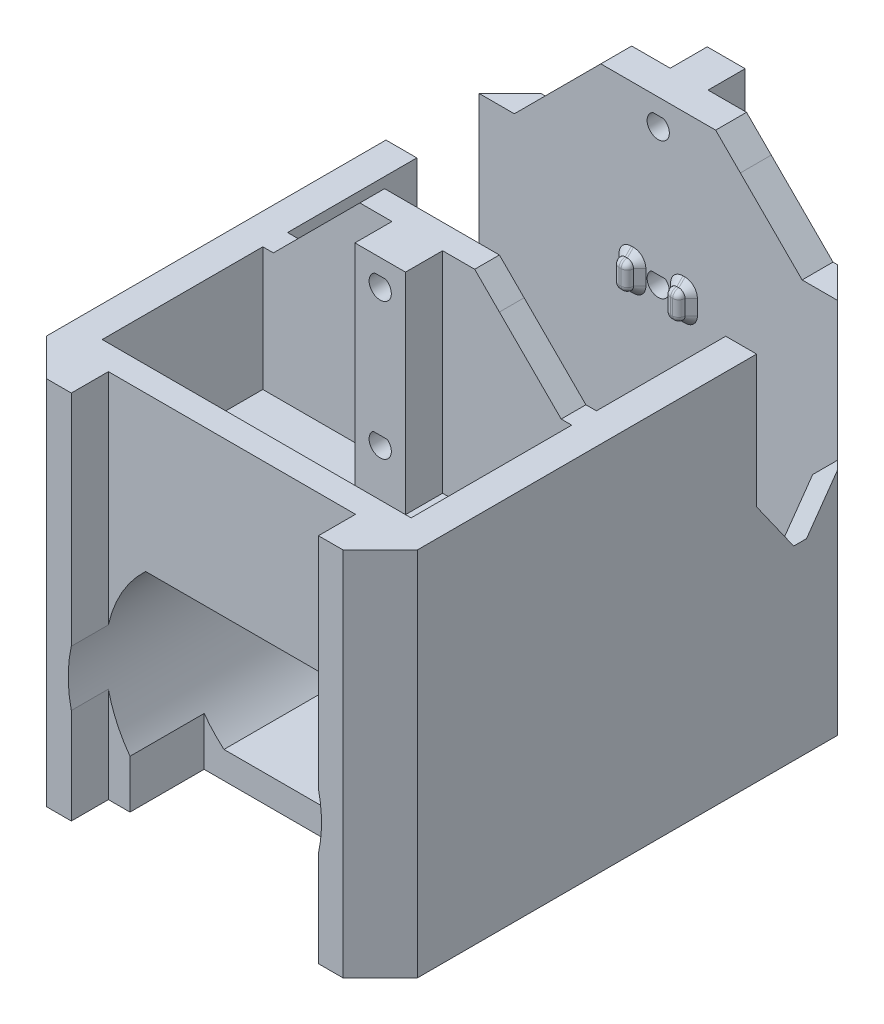
SolidWorks part; units mm, degrees
ref_plane "Front Plane" through (0, 0, 0) normal (0, 0, 1) x (1, 0, 0)
ref_plane "Top Plane" through (0, 0, 0) normal (0, 1, 0) x (1, 0, 0)
ref_plane "Right Plane" through (0, 0, 0) normal (1, 0, 0) x (0, 0, -1)
sketch "Sketch1" plane through (0, 0, 0) normal (0, 0, 1) x (1, 0, 0)
  line L1 (-15, -20) -> (15, -20)
  line L2 (-15, -20) -> (-15, 20)
  line L3 (-15, 20) -> (15, 20)
  line L4 (15, -20) -> (15, 20)
  line L5 (-15, -20) -> (15, 20) construction
  line L6 (-15, 20) -> (15, -20) construction
  point P0 (0, 0)
  dimension "D1" = 30
  dimension "D2" = 40
extrude "Boss-Extrude1" add sketch "Sketch1" along normal blind 40
sketch "Sketch2" plane through (0, 0, 40) normal (0, 0, 1) x (1, 0, 0)
  line L5 (-6.9866, -2.5) -> (6.9866, -2.5)
  line L7 (-6.6464, -17.803) -> (6.6464, -17.803)
  arc A4 (-6.9866, -2.5) -> (-6.6464, -17.803) centre (0, -10) ccw
  arc A5 (6.6464, -17.803) -> (6.9866, -2.5) centre (0, -10) ccw
  point P0 (0, -10)
  dimension "D2" = 20.5
extrude "Cut-Extrude1" cut sketch "Sketch2" against normal blind 35
sketch "Sketch4" plane through (0, 20, 0) normal (0, 1, 0) x (1, 0, 0)
  line L1 (-12.5, -37.5) -> (12.5, -37.5)
  line L2 (-12.5, -37.5) -> (-12.5, -2.5)
  line L3 (-12.5, -2.5) -> (12.5, -2.5)
  line L4 (12.5, -37.5) -> (12.5, -2.5)
  point P0 (0, -20)
  dimension "D1" = 25
  dimension "D2" = 35
extrude "Cut-Extrude3" cut sketch "Sketch4" against normal blind 20
sketch "Sketch5" plane through (0, 0, 0) normal (0, 1, 0) x (1, 0, 0)
  line L0 (12.5, -37.5) -> (12.5, -2.5) construction
  line L1 (-12.5, -2.5) -> (12.5, -2.5)
  line L2 (-12.5, -2.5) -> (-12.5, -20)
  line L3 (-12.5, -20) -> (12.5, -20)
  line L4 (12.5, -2.5) -> (12.5, -20)
extrude "Cut-Extrude4" cut sketch "Sketch5" against normal blind 20
sketch "Sketch13" plane through (0, 0, 0) normal (0, 1, 0) x (1, 0, 0)
  line L0 (12.5, -37.5) -> (12.5, -20) construction
  line L1 (-12.5, -20) -> (12.5, -20)
  line L2 (-12.5, -20) -> (-12.5, -22.0007)
  line L3 (-12.5, -22.0007) -> (12.5, -22.0007)
  line L4 (12.5, -20) -> (12.5, -22.0007)
extrude "Boss-Extrude3" add sketch "Sketch13" along normal up to surface (20 mm away) up to face at (0, 20, 20)
sketch "Sketch8" plane through (0, 0, 40) normal (0, 0, 1) x (1, 0, 0)
  line L0 (-0.5467, -9.1627) -> (0.5467, -9.1627)
  arc A3 (-0.5467, -9.1627) -> (0.5467, -9.1627) centre (0, -10.2278) ccw
extrude "Cut-Extrude5" cut sketch "Sketch8" against normal up to surface (40 mm away) up to face at (0, 0, 0)
sketch "Sketch9" plane through (0, 0, 0) normal (0, 0, -1) x (-1, 0, 0)
  line L5 (-0.5842, 4.5346) -> (0.5842, 4.5346)
  arc A0 (-0.5842, 4.5346) -> (0.5842, 4.5346) centre (0, 3.85) ccw
  dimension "D2" = 1.8
extrude "Cut-Extrude6" cut sketch "Sketch9" against normal up to surface (40 mm away) up to face at (0, -10.1897, 40)
sketch "Sketch10" plane through (0, 0, 40) normal (0, 0, 1) x (1, 0, 0)
  line L0 (15, -20) -> (15, 20) construction
  line L1 (-15, 20) -> (15, 20)
  line L2 (-15, 20) -> (-15, 10)
  line L3 (-15, 10) -> (15, 10)
  line L4 (15, 20) -> (15, 10)
  dimension "D1" = 10
extrude "Cut-Extrude9" cut sketch "Sketch10" against normal up to surface (40 mm away) up to face at (0, 3.7423, 0)
chamfer "Chamfer2" distance 3 angle 45 4 edges at (15, -5, 0) (15, -5, 40) (-15, -5, 40) (-15, -5, 0)
sketch "Sketch16" plane through (-12.5, 0, 0) normal (1, 0, 0) x (0, 0, -1)
  line L1 (-2.5, 10) -> (-9.5368, 10)
  line L2 (-2.5, 10) -> (-2.5, -4.4568)
  line L4 (-9.5368, 10) -> (-9.5368, -4.4568)
  line L5 (-9.5368, -4.4568) -> (-2.5, -4.4568)
extrude "Cut-Extrude10" cut sketch "Sketch16" against normal mid plane 57
chamfer "Chamfer3" distance 3 angle 45 2 edges at (12.5, -4.4568, 6.0184) (-12.5, -4.4568, 6.0184)
sketch "Sketch17" plane through (0, 10, 0) normal (0, 1, 0) x (1, 0, 0)
  line L0 (12.5, -37.5) -> (12.5, -22.0007) construction
  line L1 (-12.5, -37.5) -> (12.5, -37.5)
  line L2 (-12.5, -37.5) -> (-12.5, -35)
  line L3 (-12.5, -35) -> (12.5, -35)
  line L4 (12.5, -37.5) -> (12.5, -35)
  dimension "D1" = 2.5
extrude "Boss-Extrude4" add sketch "Sketch17" against normal up to surface (10 mm away) up to face at (0, 0, 29.7504)
sketch "Sketch18" plane through (0, 10, 0) normal (0, 1, 0) x (1, 0, 0)
  line L0 (-10, -40) -> (10, -40)
  line L1 (-12, -40) -> (12, -40) construction
  line L5 (-10, -40) -> (10, -40)
  line L6 (-10, -40) -> (-10, -37)
  line L7 (-10, -37) -> (10, -37)
  line L8 (10, -40) -> (10, -37)
  point P5 (0, -40)
  line M15 (-12, -40) -> (12, -40)
  dimension "D1" = 20
  dimension "D2" = 3
extrude "Cut-Extrude13" cut sketch "Sketch18" against normal up to surface (30 mm away) contours L8 L7 L6 M15 region at (0, 10, 38.5) up to face at (0, -20, 11.25)
sketch "Sketch19" plane through (0, -20, 0) normal (0, -1, 0) x (1, 0, 0)
  line L0 (-8.25, 37) -> (8.25, 37)
  line L1 (10, 37) -> (-10, 37) construction
  line L5 (-8.25, 37) -> (8.25, 37)
  line L6 (-8.25, 37) -> (-8.25, 31)
  line L7 (-8.25, 31) -> (8.25, 31)
  line L8 (8.25, 37) -> (8.25, 31)
  point P5 (0, 37)
  line M18 (10, 37) -> (-10, 37)
  dimension "D1" = 16.5
  dimension "D2" = 6
extrude "Cut-Extrude14" cut sketch "Sketch19" against normal blind 10 contours L8 L6 L7 M18 region at (0, -20, 34)
sketch "Sketch20" plane through (0, 0, 20) normal (0, 0, -1) x (-1, 0, 0)
  line L0 (10.25, -10) -> (12.5, -10)
  line L1 (-12.5, -10) -> (-10.25, -10)
  line L2 (-12.5, -10) -> (-12.5, -20)
  line L3 (-12.5, -20) -> (12.5, -20)
  line L4 (12.5, -20) -> (12.5, 10)
  line L5 (12.5, 10) -> (-12.5, 10)
  line L6 (-12.5, 10) -> (-12.5, -20)
  line L7 (-12.5, -20) -> (12.5, -20)
  line L8 (12.5, -20) -> (12.5, -10)
  line L10 (-12.5, -10) -> (-12.5, -20)
  line L11 (-12.5, -20) -> (12.5, -20)
  line L12 (12.5, -10) -> (12.5, -20)
  line L13 (-6.6464, -17.803) -> (6.6464, -17.803)
  arc A0 (6.6464, -17.803) -> (6.9866, -2.5) centre (0, -10) ccw construction
  arc A1 (6.6464, -17.803) -> (10.25, -10) centre (0, -10) ccw
  arc A2 (-6.9866, -2.5) -> (-6.6464, -17.803) centre (0, -10) ccw construction
  arc A3 (-10.25, -10) -> (-6.6464, -17.803) centre (0, -10) ccw
  line M7 (12.5, -20) -> (12.5, 10)
  line M9 (-12.5, 10) -> (-12.5, -20)
  line M10 (-12.5, -20) -> (12.5, -20)
  line M11 (6.6464, -17.803) -> (-6.6464, -17.803)
  arc M12 (-6.6464, -17.803) -> (-6.9866, -2.5) centre (0, -10) cw
  arc M14 (6.9866, -2.5) -> (6.6464, -17.803) centre (0, -10) cw
  dimension "D1" = 0
extrude "Boss-Extrude5" add sketch "Sketch20" along normal blind 8.5 contours L1 L0 M9 M10 M7 M14 M11 M12 region at (-11.375, -10.2693, 20)
sketch "Sketch22" plane through (0, 0, 11.5) normal (0, 0, -1) x (-1, 0, 0)
  line L0 (12.5, -20) -> (12.5, -10) construction
  line L1 (-12.5, -20) -> (12.5, -20)
  line L2 (-12.5, -20) -> (-12.5, -15)
  line L3 (-12.5, -15) -> (12.5, -15)
  line L4 (12.5, -20) -> (12.5, -15)
extrude "Boss-Extrude6" add sketch "Sketch22" along normal blind 1
sketch "Sketch23" plane through (0, 10, 0) normal (0, 1, 0) x (1, 0, 0)
  line L0 (-12.5, -10.5) -> (12.5, -10.5) construction
  line L3 (-6.6464, -22.0007) -> (6.6464, -22.0007)
  line L4 (6.6464, 0) -> (6.6464, -2.5)
  line L5 (-6.6464, 0) -> (-6.6464, -2.5)
  line L6 (-6.6464, -2.5) -> (0, -2.5)
  line L7 (-12.5, -22.0007) -> (12.5, -22.0007) construction
  line L8 (12.5, -22.0007) -> (-12.5, -22.0007) construction
  line L9 (-6.6464, -20) -> (6.6464, -20)
  line L10 (-12.5, -20) -> (12.5, -20) construction
  line L11 (-6.6464, 0) -> (6.6464, 0)
  line L12 (-12, 0) -> (12, 0) construction
  line L14 (14.5, -2.5) -> (-14.5, -2.5) construction
  line L15 (0, -2.5) -> (6.6464, -2.5)
  line L17 (-6.6464, -20) -> (-6.6464, -22.0007)
  line L18 (6.6464, -20) -> (6.6464, -22.0007)
  point P0 (0, -10.5)
  point P16 (0, -20)
  point P21 (0, 0)
extrude "Boss-Extrude7" add sketch "Sketch23" along normal blind 7
chamfer "Chamfer4" distance 5 angle 45 4 edges at (-6.6464, 10, 21.0004) (-6.6464, 10, 1.25) (6.6464, 10, 21.0004) (6.6464, 10, 1.25)
sketch "Sketch24" plane through (0, 0, 37) normal (0, 0, 1) x (1, 0, 0)
  line L0 (-0.4462, 15.6949) -> (0.4462, 15.6949)
  arc A0 (-0.4462, 15.6949) -> (0.4462, 15.6949) centre (0, 14.9133) ccw
  dimension "D2" = 1.8
extrude "Cut-Extrude15" cut sketch "Sketch24" against normal up to surface (37 mm away) up to face at (0, 6.4, 0)
sketch "Sketch25" plane through (0, 0, 2.5) normal (0, 0, 1) x (1, 0, 0)
  line L0 (1.5022, 4.9636) -> (2.6698, 4.9636)
  line L1 (-2.6698, 4.9636) -> (-1.5022, 4.9636)
  line L2 (-2.6698, 4.9636) -> (-2.6698, 2.7364)
  line L3 (-2.6698, 2.7364) -> (-1.5022, 2.7364)
  line L4 (2.6698, 4.9636) -> (2.6698, 2.7364)
  line L5 (-2.6698, 4.9636) -> (-1.5022, 4.4766) construction
  line L6 (-2.6698, 2.7364) -> (-1.5022, 3.2234) construction
  line L8 (-1.5022, 4.9636) -> (-1.5022, 2.7364)
  line L10 (1.5022, 4.9636) -> (1.5022, 2.7364)
  line L13 (1.5022, 3.2234) -> (2.6698, 2.7364) construction
  line L14 (1.5022, 4.4766) -> (2.6698, 4.9636) construction
  line L15 (1.5022, 2.7364) -> (2.6698, 2.7364)
  point P0 (0, 3.85)
  point P5 (0, 3.85)
extrude "Boss-Extrude8" add sketch "Sketch25" along normal blind 1
fillet "Fillet1" radius 0.5 8 edges at (1.5022, 3.85, 3.5) (2.086, 4.9636, 3.5) (2.6698, 3.85, 3.5) (2.086, 2.7364, 3.5) (-2.6698, 3.85, 3.5) (-2.086, 2.7364, 3.5) (-1.5022, 3.85, 3.5) (-2.086, 4.9636, 3.5)
fillet "Fillet2" radius 0.5 16 edges at (2.6698, 2.7364, 2.75) (1.5022, 2.7364, 2.75) (1.5022, 4.9636, 2.75) (2.6698, 4.9636, 2.75) (-1.5022, 2.7364, 2.75) (-2.6698, 2.7364, 2.75) (-2.6698, 4.9636, 2.75) (-1.5022, 4.9636, 2.75) (2.5234, 2.8828, 3.3536) (1.6486, 2.8828, 3.3536) (1.6486, 4.8172, 3.3536) (2.5234, 4.8172, 3.3536) (-1.6486, 2.8828, 3.3536) (-2.5234, 2.8828, 3.3536) (-2.5234, 4.8172, 3.3536) (-1.6486, 4.8172, 3.3536)
chamfer "Chamfer5" distance 0.5 angle 45 16 edges at (1.5022, 3.85, 2.5) (1.6486, 2.8828, 2.5) (1.6486, 4.8172, 2.5) (2.086, 2.7364, 2.5) (2.086, 4.9636, 2.5) (2.5234, 2.8828, 2.5) (2.5234, 4.8172, 2.5) (2.6698, 3.85, 2.5) (-2.6698, 3.85, 2.5) (-2.5234, 2.8828, 2.5) (-2.5234, 4.8172, 2.5) (-2.086, 2.7364, 2.5) (-2.086, 4.9636, 2.5) (-1.6486, 2.8828, 2.5) (-1.6486, 4.8172, 2.5) (-1.5022, 3.85, 2.5)
chamfer "Chamfer6" distance 2 angle 45 4 edges at (-6.6464, 17, 1.25) (-6.6464, 17, 21.0004) (6.6464, 17, 1.25) (6.6464, 17, 21.0004)
sketch "Sketch26" plane through (0, 0, 22.0007) normal (0, 0, 1) x (1, 0, 0)
  line L0 (-10, 10) -> (10, 10) construction
  line L2 (2.0482, 17) -> (2.0482, 0)
  line L3 (2.0482, 0) -> (-2.0482, 0)
  line L4 (-2.0482, 17) -> (-2.0482, 0)
  line L5 (-0.5842, 4.5346) -> (0.5842, 4.5346) construction
  line L6 (-0.4462, 15.6949) -> (0.4462, 15.6949) construction
  line L7 (-12.5, 0) -> (12.5, 0) construction
  line L8 (-2.0482, 17) -> (2.0482, 17)
  line L9 (-4.6464, 17) -> (4.6464, 17) construction
  line L10 (-0.5842, 4.5346) -> (0.5842, 4.5346)
  line L11 (-0.4462, 15.6949) -> (0.4462, 15.6949)
  arc A0 (-0.5842, 4.5346) -> (0.5842, 4.5346) centre (0, 3.85) ccw construction
  arc A1 (-0.4462, 15.6949) -> (0.4462, 15.6949) centre (0, 14.9133) ccw construction
  arc A2 (-0.5842, 4.5346) -> (0.5842, 4.5346) centre (0, 3.85) ccw
  arc A3 (-0.4462, 15.6949) -> (0.4462, 15.6949) centre (0, 14.9133) ccw
  point P0 (0, 10)
extrude "Boss-Extrude9" add sketch "Sketch26" along normal blind 3
sketch "Sketch27" plane through (0, 0, 0) normal (0, 0, -1) x (-1, 0, 0)
  line L0 (-4.6464, 17) -> (4.6464, 17) construction
  line L1 (-1.5334, 12.8267) -> (1.5334, 12.8267)
  line L2 (-1.5334, 12.8267) -> (-1.5334, 17)
  line L3 (-1.5334, 17) -> (1.5334, 17)
  line L4 (1.5334, 12.8267) -> (1.5334, 17)
  line L7 (-0.4462, 15.6949) -> (0.4462, 15.6949) construction
  line L8 (-0.4462, 15.6949) -> (0.4462, 15.6949)
  arc A0 (-0.4462, 15.6949) -> (0.4462, 15.6949) centre (0, 14.9133) ccw construction
  arc A1 (-0.4462, 15.6949) -> (0.4462, 15.6949) centre (0, 14.9133) ccw
  point P0 (0, 14.9133)
extrude "Boss-Extrude10" add sketch "Sketch27" along normal blind 3
chamfer "Chamfer7" distance 2.8 angle 47 1 edges at (0, 12.8267, 0) first distance on face at (0, 8.8324, 0)
chamfer "Chamfer8" distance 3 angle 45 4 edges at (-13.75, -6.2068, 9.5368) (-13.5, -6.4568, 2.5) (13.5, -6.4568, 2.5) (13.75, -6.2068, 9.5368)
